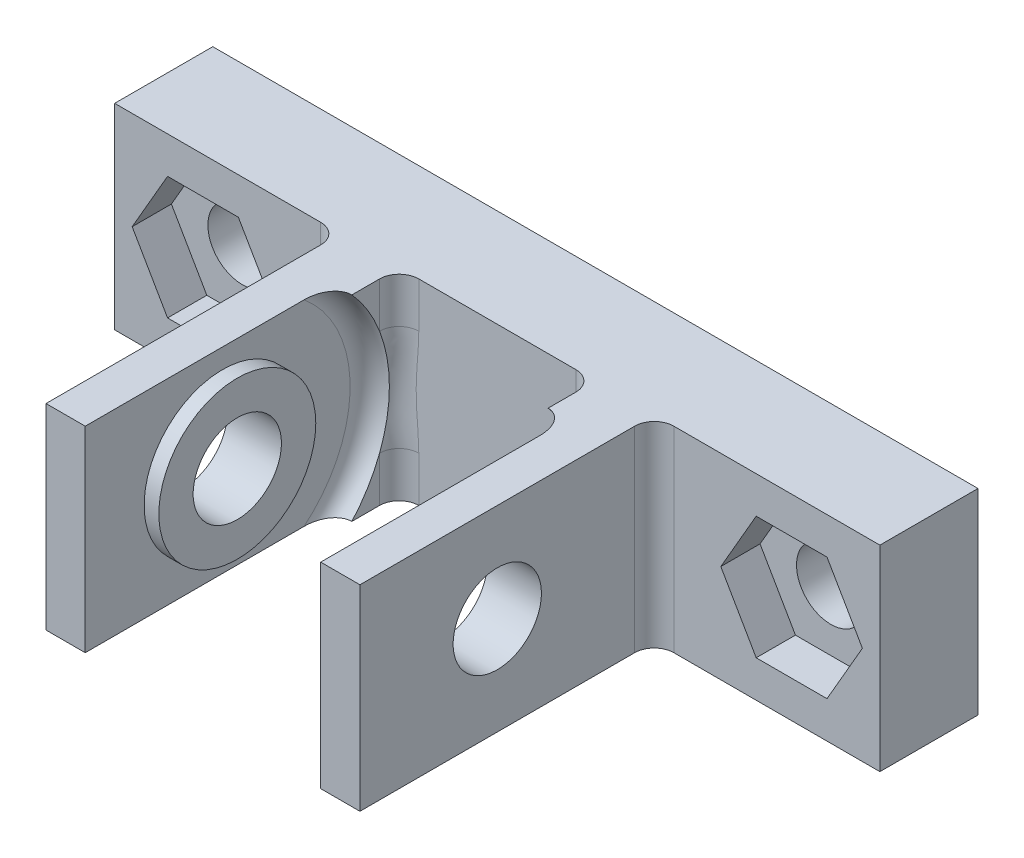
SolidWorks part; units mm, degrees
ref_plane "Front Plane" through (0, 0, 0) normal (0, 0, 1) x (1, 0, 0)
ref_plane "Top Plane" through (0, 0, 0) normal (0, 1, 0) x (1, 0, 0)
ref_plane "Right Plane" through (0, 0, 0) normal (1, 0, 0) x (0, 0, -1)
sketch "Sketch1" plane through (0, 0, 0) normal (0, 1, 0) x (1, 0, 0)
  line L0 (0, 0) -> (0, -20.0709) construction
  line L1 (-8, 0) -> (8, 0)
  line L2 (8, 0) -> (8, -20)
  line L3 (8, -20) -> (5, -20)
  line L4 (5, -20) -> (5, -5)
  line L5 (5, -5) -> (-5, -5)
  line L6 (-5, -20) -> (-5, -5)
  line L7 (-8, -20) -> (-5, -20)
  line L8 (-8, 0) -> (-8, -20)
  line L9 (5, -20) -> (5, -5)
  point P9 (0, -5)
  dimension "D1" = 5
  dimension "D2" = 3
  dimension "D3" = 15
  dimension "D4" = 5
extrude "Boss-Extrude1" add sketch "Sketch1" along normal blind 10 contours L1 L0 L5 L4 L3 L2 | L0 L1 L8 L7 L6 L5 region at (5.3235, 0, 7.7941) region at (-5.3235, 0, 7.7941)
sketch "Sketch2" plane through (8, 0, 0) normal (1, 0, 0) x (0, 0, -1)
  line L0 (-20, 5) -> (0, 5) construction
  line L1 (-20, 10) -> (-20, 0) construction
  line L2 (0, 10) -> (0, 0) construction
  circle A0 centre (-13, 5) radius 2.25
  dimension "D1" = 4.5
  dimension "D2" = 13
extrude "Cut-Extrude1" cut sketch "Sketch2" against normal through all contours A0
sketch "Sketch3" plane through (0, 10, 0) normal (0, 1, 0) x (1, 0, 0)
  line L1 (-19.5, -5) -> (19.5, -5)
  line L2 (0, 0) -> (0, -5) construction
  line L3 (-19.5, 0) -> (19.5, 0)
  line L4 (19.5, -5) -> (19.5, 0)
  line L5 (-8, 0) -> (8, 0) construction
  line L7 (-19.5, -5) -> (-19.5, 0)
  line L8 (5, -5) -> (-5, -5) construction
  dimension "D1" = 19.5
extrude "Boss-Extrude2" add sketch "Sketch3" against normal through all
sketch "Sketch4" plane through (0, 0, 5) normal (0, 0, 1) x (1, 0, 0)
  line L0 (-19.5, 5) -> (-8, 5) construction
  line L1 (-19.5, 0) -> (-19.5, 10) construction
  line L2 (-8, 10) -> (-8, 0) construction
  line L3 (-15, 0) -> (-15, 10) construction
  line L6 (0, 0) -> (0, 10) construction
  line L7 (5, 0) -> (-5, 0) construction
  line L8 (5, 10) -> (-5, 10) construction
  line L9 (15, 0) -> (15, 10) construction
  line L10 (19.5, 5) -> (8, 5) construction
  line L11 (-15, 0) -> (-15, 10) construction
  circle A0 centre (-15, 5) radius 1.75
  circle A1 centre (15, 5) radius 1.75
  dimension "D1" = 3.5
  dimension "D2" = 15
extrude "Cut-Extrude2" cut sketch "Sketch4" against normal through all
sketch "Sketch6" plane through (-5, 0, 0) normal (1, 0, 0) x (0, 0, -1)
  line L0 (-13, 12.5) -> (-20.5, 12.5)
  line L1 (-20.5, 12.5) -> (-20.5, 5)
  line L2 (-20.5, 5) -> (-20.5, -2.5)
  line L3 (-20.5, -2.5) -> (-13, -2.5)
  arc A0 (-13, -2.5) -> (-13, 12.5) centre (-13, 5) ccw
  circle A1 centre (-13, 5) radius 2.25 construction
  dimension "D1" = 15
extrude "Cut-Extrude3" cut sketch "Sketch6" against normal blind 1
sketch "Sketch5" plane through (-6, 0, 0) normal (1, 0, 0) x (0, 0, -1)
  circle A0 centre (-13, 5) radius 4
  circle A1 centre (-13, 5) radius 2.25
  circle A2 centre (-13, 5) radius 2.25 construction
  dimension "D1" = 8
extrude "Boss-Extrude3" add sketch "Sketch5" along normal blind 0.75
mirror "Mirror1" about plane through (0, 0, 0) normal (1, 0, 0) of "Boss-Extrude3", "Cut-Extrude3"
fillet "Fillet1" radius 1 6 edges at (-6, 5, 5.5) (6, 5, 5.5) (5, 5, 5) (-5, 5, 5) (8, 5, 5) (-8, 5, 5)
sketch "Sketch7" plane through (0, 0, 5) normal (0, 0, 1) x (1, 0, 0)
  line L0 (0, 10) -> (0, 0) construction
  line L1 (16.8042, 8.125) -> (13.1958, 8.125)
  line L2 (13.1958, 8.125) -> (11.3916, 5)
  line L3 (11.3916, 5) -> (13.1958, 1.875)
  line L4 (13.1958, 1.875) -> (16.8042, 1.875)
  line L5 (16.8042, 1.875) -> (18.6084, 5)
  line L6 (18.6084, 5) -> (16.8042, 8.125)
  line L7 (4, 10) -> (-4, 10) construction
  line L8 (-18.6084, 5) -> (-16.8042, 8.125)
  line L9 (-16.8042, 1.875) -> (-18.6084, 5)
  line L10 (-13.1958, 1.875) -> (-16.8042, 1.875)
  line L11 (-11.3916, 5) -> (-13.1958, 1.875)
  line L12 (-13.1958, 8.125) -> (-11.3916, 5)
  line L13 (-16.8042, 8.125) -> (-13.1958, 8.125)
  line L14 (18.6084, 5) -> (16.8042, 8.125)
  circle A0 centre (15, 5) radius 3.125 construction
  circle A1 centre (-15, 5) radius 3.125 construction
  circle M5 centre (15, 5) radius 1.75
  dimension "D1" = 6.25
extrude "Cut-Extrude4" cut sketch "Sketch7" against normal blind 2 contours L13 L8 L9 L10 L11 L12 | L5 L6 L1 L2 L3 L4 M5 | M5 region at (17.6236, 6.5148, 5) region at (-15, 5, 5) region at (15, 5, 5)
equation "\"X-ROD-SPACING\"=45"
equation "\"Y-ROD-SPACING\"=75"
equation "\"Z-ROD-SPACING\"=17.5"
equation "\"Y-BED-OFFSET\"=2"
equation "\"Y-BED-ROD-INSET\"=3.5"
equation "\"Y-BED-SCREW-SPACING\"=209"
equation "\"Y-BED-SCREW-CUTOUT-SLOT-HEIGHT\"=2.5"
equation "\"T-SLOT-NUT-FILLET-RADIUS\"=0.5"
equation "\"T-SLOT-SCREW-SHAFT-RADIUS\"=1.55"
equation "\"T-SLOT-SCREW-SHAFT-CUTOUT-LENGTH\"=11"
equation "\"T-SLOT-NUT-DEPTH\"=3.5"
equation "\"T-SLOT-NUT-WIDTH\"=2.85"
equation "\"T-SLOT-NUT-END-DISTANCE\"=8"
equation "\"ACRYLIC-THICKNESS\"=10"
equation "\"ACRYLIC-THICKNESS2\"=4.5"
equation "\"ACRYLIC-TAB-CUTOUT-SIZE\"=\"ACRYLIC-THICKNESS\"+\"ACRYLIC-TAB-TOLERANCE\"*2"
equation "\"ACRYLIC-TAB-TOLERANCE\"=-.05"
equation "\"KERF\"=0.075"
equation "\"ACRYLIC-THICKNESS-TAB-CUTOUT-WIDTH\"=\"ACRYLIC-THICKNESS\"-\"KERF\"*2"
equation "\"ACRYLIC-THICKNESS-TAB-CUTOUT-HEIGHT\"=\"ACRYLIC-TAB-WIDTH\"-\"KERF\"*4"
equation "\"ACRYLIC-THICKNESS2-TAB-CUTOUT-WIDTH\"=\"ACRYLIC-THICKNESS2\"-\"KERF\"*2"
equation "\"ACRYLIC-THICKNESS2-TAB-CUTOUT-HEIGHT\"=\"ACRYLIC-TAB-WIDTH\"-\"KERF\"*4"
equation "\"ACRYLIC-TAB-WIDTH\"=\"ACRYLIC-THICKNESS\""
equation "\"ACRYLIC-M3-HOLE\"=2.9"
equation "\"SMOOTHROD-CAP-SCREW-DISTANCE\"=20"
equation "\"FRAME-WIDTH-INNER\"=370"
equation "\"NEMA17-HOLE-SPACING\"=31"
equation "\"NEMA17-CENTRAL-CUTOUT\"=22.5"
equation "\"Z-BRACKET-REACH\"=57"
equation "\"Z-ROD-INSET\"=13.5"
equation "\"TOP-BRACKET-SPACING\"=40"
equation "\"SMOOTHROD-X-LENGTH\"=350"
equation "\"SMOOTHROD-Y-LENGTH\"=350"
equation "\"SMOOTHROD-Z-LENGTH\"=350"
equation "\"SMOOTHROD-TIGHTENING-HEADROOM\"=.25"
equation "\"LEADSCREW-Z-LENGTH\"=300"
equation "\"SCREW-LENGTH-FRAME\"=\"ACRYLIC-THICKNESS\" + 10"
equation "\"SCREW-LENGTH-MOTOR\"=\"ACRYLIC-THICKNESS\" + 5"
equation "\"SCREW-LENGTH-EXTRUDER\"=28"
equation "\"SCREW-HEAD-RADIUS\"=6"
equation "\"PRINTED-M3-HOLE\"=3.5"
equation "\"PRINTED-X-SMOOTHROD-DIAMETER\"=8.8"
equation "\"PRINTED-X-SMOOTHROD-CUTOUT\"=10"
equation "\"PRINTED-X-BASE-HEIGHT\"=10"
equation "\"PRINTED-LM8UU-CUTOUT-SIZE\"=15.5"
equation "\"PRINTED-LM8UU-CUTOUT-LENGTH\"=24.5"
equation "\"PRINTED-X-IDLER-HEIGHT\"=16"
equation "\"PRINTED-M3-NUT-AF\"=6.25"
equation "\"PSU-MOUNTING-WIDTH\"=95"
equation "\"PSU-MOUNTING-HEIGHT\"=177"
equation "\"Y-BELT-TO-ROD-DISTANCE\"=20"
equation "\"SPOOL-HOLDER-ROD-SPACING\"=150"
equation "\"ACRYLIC-X-CARRIAGE-WIDTH\"=55"
equation "\"ACRYLIC-X-CARRIAGE-HEIGHT\"=75"
equation "\"ACRYLIC-X-CARRIAGE-LM8UU-CUTOUT-WIDTH\"=24.25"
equation "\"ACRYLIC-X-CARRIAGE-LM8UU-CUTOUT-HEIGHT\"=11.0"
equation "\"ACRYLIC-X-CARRIAGE-SCREW-SPACING-X\"=15"
equation "\"ACRYLIC-X-CARRIAGE-SCREW-SPACING-Y\"=33"
equation "\"ACRYLIC-X-CARRIAGE-CENTER-TAB-SPACING\"=14"
equation "\"ACRYLIC-X-CARRIAGE-EXTRUDER-OFFSET\"=26"
equation "\"ACRYLIC-X-CARRIAGE-EXTRUDER-ANGLE\"=90"
equation "\"ACRYLIC-X-CARRIAGE-EXTRUDER-SHELF-DEPTH\"=\"ACRYLIC-X-CARRIAGE-EXTRUDER-OFFSET\" + 28"
equation "\"ACRYLIC-X-CARRIAGE-EXTRUDER-BRACE-SPACING\"=23"
equation "\"ACRYLIC-X-CARRIAGE-EXTRUDER-BRACE-TAB-OFFSET\"=20"
equation "\"ACRYLIC-X-CARRIAGE-EXTRUDER-BRACE-HEIGHT\"=35"
equation "\"ACRYLIC-X-CARRIAGE-EXTRUDER-BRACE-SCREW-SPACING\"=22"
equation "\"ACRYLIC-X-CARRIAGE-DUAL-WIDTH-MULTIPLIER\"=1.65"
equation "\"ACRYLIC-X-CARRIAGE-DUAL-HOTEND-SPACING\"=42"
equation "\"ACRYLIC-X-CARRIAGE-DUAL-WIDTH\"=75"
equation "\"ACRYLIC-X-CARRIAGE-DUAL-FAN-OFFSET\"=52"
equation "\"ACRYLIC-X-CARRIAGE-DUAL-FAN-HEIGHT\"=20"
equation "\"ACRYLIC-X-CARRIAGE-DUAL-HOTEND-SEPARATION\"=36"
equation "\"ACRYLIC-X-CARRIAGE-DUAL-MOUNT-PLATE-DEPTH\"=75"
equation "\"ACRYLIC-X-CARRIAGE-DUAL-MOUNT-BRACE-WIDTH\"=33"
equation "\"ACRYLIC-X-CARRIAGE-DUAL-MOUNT-SCREW-WIDTH\"=40"
equation "\"BLOWER-FAN-WIDTH\"=15"
equation "\"D1@Sketch7\"=\"PRINTED-M3-NUT-AF\""
